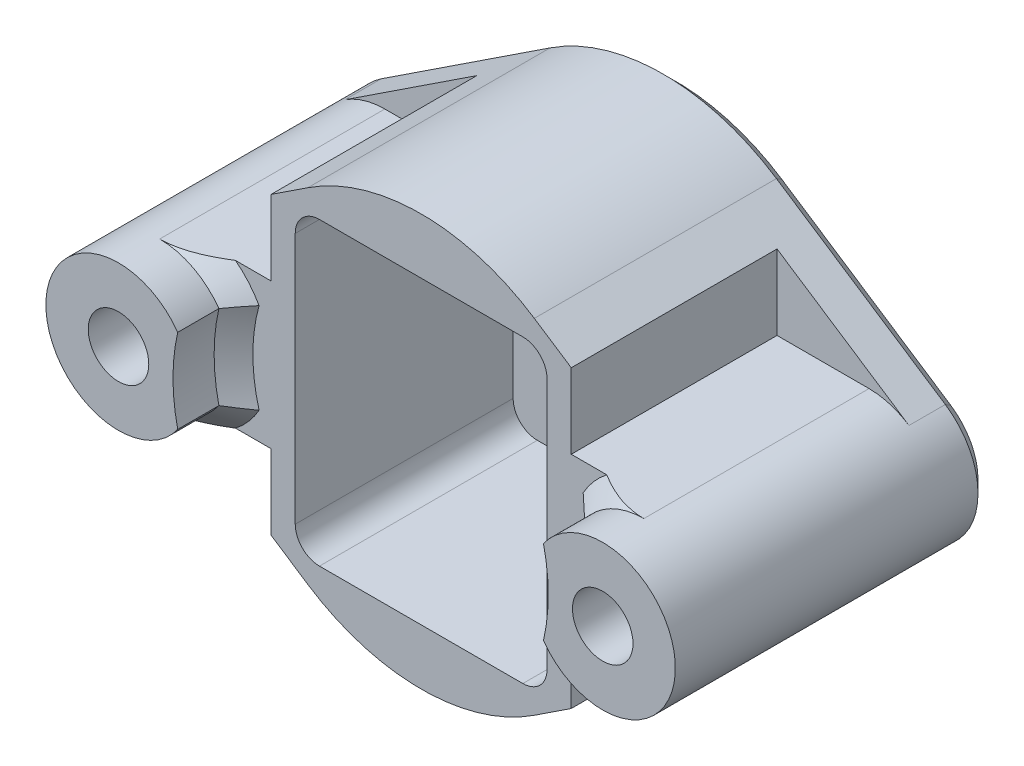
SolidWorks part; units mm, degrees
material "ABS"
ref_plane "Front" through (0, 0, 0) normal (0, 0, 1) x (1, 0, 0)
ref_plane "Top" through (0, 0, 0) normal (0, 1, 0) x (1, 0, 0)
ref_plane "Right" through (0, 0, 0) normal (1, 0, 0) x (0, 0, -1)
sketch "Эскиз2" plane through (0, 0, 0) normal (0, 0, 1) x (1, 0, 0)
  line L0 (4.675, 7.0989) -> (11.65, 2.5055)
  line L1 (11.65, -2.5055) -> (4.675, -7.0989)
  line L2 (-10, 0) -> (10, 0) construction
  line L3 (-4.675, -7.0989) -> (-11.65, -2.5055)
  line L4 (-4.675, 7.0989) -> (-11.65, 2.5055)
  line L5 (0, -8.5) -> (0, 8.5) construction
  circle A0 centre (10, 0) radius 1.1 construction
  arc A1 (11.65, 2.5055) -> (11.65, -2.5055) centre (10, 0) cw
  arc A3 (4.675, -7.0989) -> (-4.675, -7.0989) centre (0, 0) cw
  arc A5 (-11.65, -2.5055) -> (-11.65, 2.5055) centre (-10, 0) cw
  arc A6 (4.675, 7.0989) -> (-4.675, 7.0989) centre (0, 0) ccw
  circle A7 centre (0, 4.5) radius 1
  circle A9 centre (0, -4.5) radius 1
  circle A10 centre (0, 0) radius 1.7
  circle A11 centre (-10, 0) radius 1.1 construction
  point P12 (0, 0)
  point P15 (10, 0)
  point P20 (-10, 0)
  dimension "D1" = 2.2
  dimension "D2" = 3
  dimension "D4" = 17
  dimension "D5" = 2
  dimension "D7" = 3.4
  dimension "D3" = 20
  dimension "D6" = 9
extrude "Основание" add sketch "Эскиз2" along normal blind 2
sketch "Эскиз3" plane through (0, 0, 2) normal (0, 0, 1) x (1, 0, 0)
  line L0 (11.65, 2.5055) -> (4.675, 7.0989) construction
  line L1 (6.2, 6.0946) -> (6.2, -6.0946)
  line L2 (4.2, 6.2) -> (-4.2, 6.2)
  line L3 (5.2, 5.2) -> (5.2, -5.2)
  line L4 (4.2, -6.2) -> (-4.2, -6.2)
  line L5 (-5.2, 5.2) -> (-5.2, -5.2)
  line L6 (5.2, 6.2) -> (-5.2, -6.2) construction
  line L7 (5.2, -6.2) -> (-5.2, 6.2) construction
  line L8 (-6.2, -6.0946) -> (-6.2, 6.0946)
  line L9 (6.2, 6.0946) -> (4.675, 7.0989)
  line L10 (-4.675, 7.0989) -> (-11.65, 2.5055) construction
  line L11 (-6.2, 6.0946) -> (-4.675, 7.0989)
  line L12 (4.675, -7.0989) -> (11.65, -2.5055) construction
  line L13 (6.2, -6.0946) -> (4.675, -7.0989)
  line L14 (-11.65, -2.5055) -> (-4.675, -7.0989) construction
  line L15 (-6.2, -6.0946) -> (-4.675, -7.0989)
  arc A1 (-4.2, -6.2) -> (-5.2, -5.2) centre (-4.2, -5.2) cw
  arc A6 (4.2, -6.2) -> (5.2, -5.2) centre (4.2, -5.2) ccw
  arc A7 (5.2, 5.2) -> (4.2, 6.2) centre (4.2, 5.2) ccw
  arc A8 (-4.2, 6.2) -> (-5.2, 5.2) centre (-4.2, 5.2) ccw
  arc A9 (-4.675, -7.0989) -> (4.675, -7.0989) centre (0, 0) ccw
  circle A10 centre (0, 0) radius 7.6843 construction
  arc A11 (-4.675, 7.0989) -> (4.675, 7.0989) centre (0, 0) cw
  arc A12 (4.675, 7.0989) -> (-4.675, 7.0989) centre (0, 0) ccw construction
  arc A13 (-4.675, -7.0989) -> (4.675, -7.0989) centre (0, 0) ccw construction
  dimension "D1" = 12.4
  dimension "D3" = 1
  dimension "D4" = 1
  dimension "D2" = 10.4
extrude "Стенки" add sketch "Эскиз3" along normal offset from surface (8.5 mm away) 10.5 up to face at (0, 0, 0)
sketch "Эскиз4" plane through (0, 0, 2) normal (0, 0, 1) x (1, 0, 0)
  line L0 (5.2, -5.2) -> (5.2, 5.2) construction
  line L1 (-4.2, -6.2) -> (4.2, -6.2)
  line L2 (-5.2, -5.2) -> (-5.2, 5.2)
  line L3 (-4.2, 6.2) -> (4.2, 6.2)
  line L4 (5.2, -5.2) -> (5.2, 5.2)
  line L5 (-5.2, -6.2) -> (5.2, 6.2) construction
  line L6 (-5.2, 6.2) -> (5.2, -6.2) construction
  arc A0 (4.2, -6.2) -> (5.2, -5.2) centre (4.2, -5.2) ccw
  arc A1 (4.2, 6.2) -> (5.2, 5.2) centre (4.2, 5.2) cw
  arc A2 (-4.2, 6.2) -> (-5.2, 5.2) centre (-4.2, 5.2) ccw
  arc A3 (-5.2, -5.2) -> (-4.2, -6.2) centre (-4.2, -5.2) ccw
  arc A4 (4.2, -6.2) -> (5.2, -5.2) centre (4.2, -5.2) ccw construction
  point P0 (0, 0)
extrude "Вырез дополнительный" cut sketch "Эскиз4" against normal blind 0.5
sketch "Эскиз5" plane through (0, 0, 1.5) normal (0, 0, 1) x (1, 0, 0)
  circle A0 centre (0, 0) radius 2.25
  dimension "D1" = 4.5
extrude "Вырез под ободок вала" cut sketch "Эскиз5" against normal blind 0.9
chamfer "Фаска под винты М1.6" distance 0.8 angle 45 2 edges at (-1, -4.5, 0) (1, 4.5, 0)
chamfer "Фаска1" distance 0.5 angle 45 9 edges at (1.7, 0, 0) (-8.1625, 4.8022, 0) (-13, 0, 0) (-8.1625, -4.8022, 0) (8.1625, -4.8022, 0) (13, 0, 0) (8.1625, 4.8022, 0) (0, -8.5, 0) (0, 8.5, 0)
sketch "Эскиз6" plane through (0, 0, 2) normal (0, 0, 1) x (1, 0, 0)
  line L0 (6.2, 3) -> (10, 3)
  line L1 (6.2, -6.0946) -> (6.2, 6.0946) construction
  line L2 (6.2, -3) -> (10, -3)
  line L3 (6.2, 3) -> (6.2, -3)
  line L4 (-6.2, -3) -> (-6.2, 3)
  line L5 (-6.2, 6.0946) -> (-6.2, -6.0946) construction
  line L6 (-6.2, 3) -> (-10, 3)
  line L7 (-6.2, -3) -> (-10, -3)
  arc A2 (10, 3) -> (10, -3) centre (10, 0) cw
  arc A3 (11.65, -2.5055) -> (11.65, 2.5055) centre (10, 0) ccw construction
  arc A4 (-10, 3) -> (-10, -3) centre (-10, 0) ccw
  circle A5 centre (10, 0) radius 1.25
  circle A6 centre (-10, 0) radius 1.25
  arc A9 (-11.65, 2.5055) -> (-11.65, -2.5055) centre (-10, 0) ccw construction
  dimension "D1" = 2.5
extrude "Стойки основание" add sketch "Эскиз6" along normal up to surface (8.5 mm away) up to face at (0, 0, 10.5)
sketch "Эскиз7" plane through (0, 0, 10.5) normal (0, 0, 1) x (1, 0, 0)
  circle A0 centre (10, 0) radius 1.25
  circle A1 centre (10, 0) radius 3
  circle A2 centre (-10, 0) radius 1.25
  circle A3 centre (-10, 0) radius 3
  circle A4 centre (-10, 0) radius 1.25 construction
  arc A5 (-10, 3) -> (-10, -3) centre (-10, 0) ccw construction
  circle A6 centre (10, 0) radius 1.25 construction
  arc A7 (10, -3) -> (10, 3) centre (10, 0) ccw construction
extrude "Крепёжные стойки" add sketch "Эскиз7" along normal offset from surface (2.5 mm away) 11 up to face at (8.5216, 3.6803, 2) offset beyond the face yes
sketch "Эскиз8" plane through (0, 0, 10.5) normal (0, 0, 1) x (1, 0, 0)
  line L0 (8.75, -1.1635) -> (8.75, 1.0264) construction
  line L1 (7.75, -0.8896) -> (7.75, 1.1719) construction
  circle A0 centre (0, 0) radius 7.75
  circle A1 centre (10, 0) radius 1.25 construction
  dimension "D1" = 15.5
  dimension "D2" = 1
extrude "Вырез под корпус двигателя" cut sketch "Эскиз8" along normal through all
chamfer "Фаска2" distance 0.8 angle 45 6 edges at (-8.6229, -2.6653, 10.5) (-8.6229, 2.6653, 10.5) (-7.75, 0, 10.5) (8.6229, -2.6653, 10.5) (8.6229, 2.6653, 10.5) (7.75, 0, 10.5)
